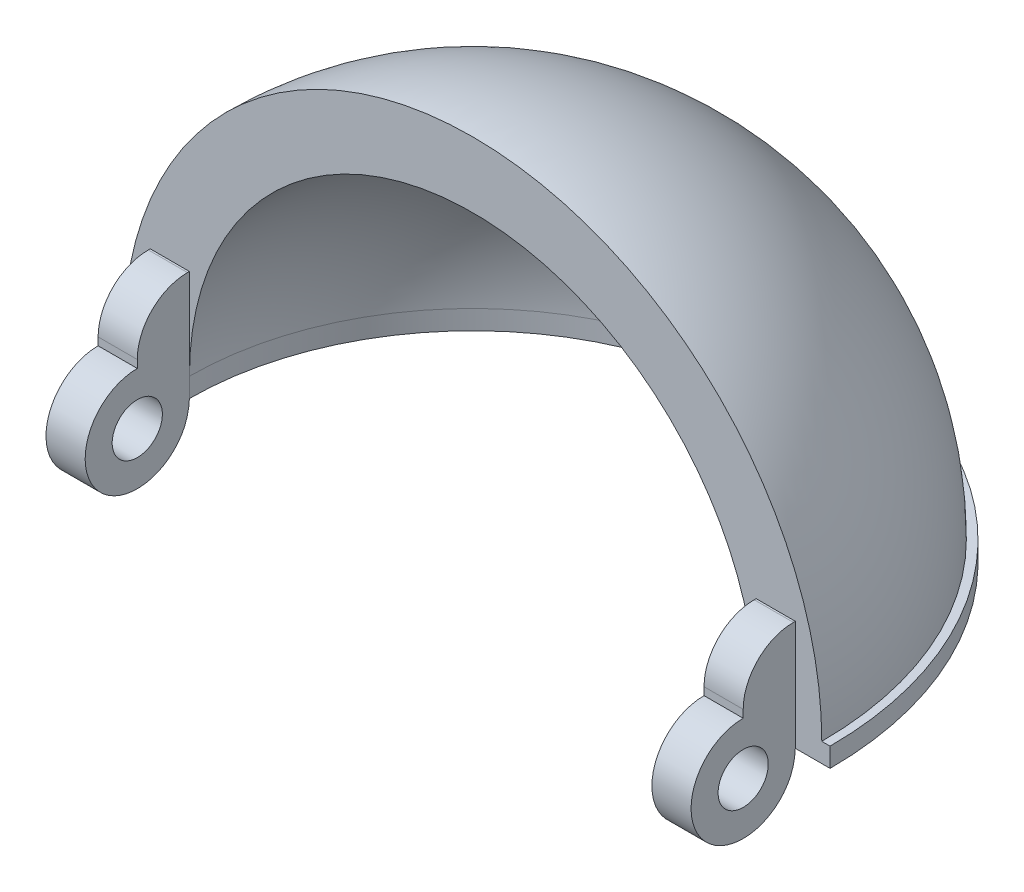
SolidWorks part; units mm, degrees
ref_plane "Front Plane" through (0, 0, 0) normal (0, 0, 1) x (1, 0, 0)
ref_plane "Top Plane" through (0, 0, 0) normal (0, 1, 0) x (1, 0, 0)
ref_plane "Right Plane" through (0, 0, 0) normal (1, 0, 0) x (0, 0, -1)
sketch "Sketch1" plane through (0, 0, 0) normal (0, 1, 0) x (1, 0, 0)
  line L2 (-18.4463, 0) -> (28.559, 0) construction
  line L4 (-18.4463, 0) -> (-13.5837, 0)
  line L8 (23.6964, 0) -> (28.559, 0)
  arc A0 (-18.4463, 0) -> (28.559, 0) centre (5.0564, 0) cw
  arc A1 (-13.5837, 0) -> (23.6964, 0) centre (5.0564, 0) cw
extrude "Boss-Extrude1" add sketch "Sketch1" along normal blind 1.27
sketch "Sketch4" plane through (0, 1.27, 0) normal (0, 1, 0) x (1, 0, 0)
  line L0 (-18.4463, 0) -> (-13.5837, 0) construction
  line L1 (23.6964, 0) -> (28.559, 0) construction
  line L2 (23.6964, 0) -> (28.0144, 0)
  line L3 (-17.9017, 0) -> (-13.5837, 0)
  line L4 (-17.9017, 0) -> (28.0144, 0) construction
  arc A0 (-13.5837, 0) -> (23.6964, 0) centre (5.0564, 0) cw
  arc A1 (-17.9017, 0) -> (28.0144, 0) centre (5.0564, 0) cw
  dimension "D1" = 4.318
  dimension "D2" = 4.318
revolve "Revolve3" add sketch "Sketch4" angle 90 about L4
sketch "Sketch6" plane through (0, 0, 0) normal (0, 0, 1) x (1, 0, 0)
  line L1 (23.6964, 0) -> (28.559, 0)
  line L2 (23.6964, 0) -> (23.6964, 1.27)
  line L3 (23.6964, 1.27) -> (28.559, 1.27)
  line L4 (28.559, 0) -> (28.559, 1.27)
  line L5 (-18.4463, 1.27) -> (-13.5837, 1.27)
  line L6 (-18.4463, 1.27) -> (-18.4463, 0)
  line L7 (-18.4463, 0) -> (-13.5837, 0)
  line L8 (-13.5837, 1.27) -> (-13.5837, 0)
extrude "Boss-Extrude3" add sketch "Sketch6" along normal blind 7.9355 contours L8 L5 L6 L7 | L3 L4 L1 L2 region at (-16.015, 0.635, 0)
sketch "Sketch10" plane through (0, 1.27, 0) normal (0, 1, 0) x (1, 0, 0)
  line L1 (-18.4463, -7.9355) -> (-13.5837, -7.9355)
  line L2 (-18.4463, -7.9355) -> (-18.4463, 0)
  line L3 (-18.4463, 0) -> (-13.5837, 0)
  line L4 (-13.5837, -7.9355) -> (-13.5837, 0)
  line L5 (23.6964, 0) -> (28.559, 0)
  line L6 (23.6964, 0) -> (23.6964, -7.9355)
  line L7 (23.6964, -7.9355) -> (28.559, -7.9355)
  line L8 (28.559, 0) -> (28.559, -7.9355)
extrude "Boss-Extrude4" add sketch "Sketch10" along normal blind 3.81 and the other way blind 6.35
fillet "Fillet7" radius 5.08 1 edges at (-16.015, 5.08, 7.9355) type face fillet first side face at (-16.015, 0, 7.9355) second side face at (-16.3286, 5.08, 3.1742)
fillet "Fillet10" radius 5.08 1 edges at (26.1277, 5.08, 7.9355) type face fillet first side face at (26.4413, 5.08, 3.1742) second side face at (26.1277, 0, 7.9355)
sketch "Sketch13" plane through (-18.4463, 0, 0) normal (-1, 0, 0) x (0, 0, 1)
  line L1 (0, 5.08) -> (2.8555, 5.08) construction
  circle A0 centre (3.4286, 0) radius 1.651
  dimension "D1" = 3.302
  dimension "D2" = 5.08
extrude "Cut-Extrude2" cut sketch "Sketch13" against normal blind 55.372
sketch "Sketch14" plane through (0, 5.08, 0) normal (0, 1, 0) x (1, 0, 0)
  line L1 (28.559, 0) -> (26.273, 0)
  line L2 (28.559, 0) -> (28.559, -11.3681)
  line L3 (28.559, -11.3681) -> (26.273, -11.3681)
  line L4 (26.273, 0) -> (26.273, -11.3681)
  line L5 (-18.4463, 0) -> (-16.1603, 0)
  line L6 (-18.4463, 0) -> (-18.4463, -11.3681)
  line L7 (-18.4463, -11.3681) -> (-16.1603, -11.3681)
  line L8 (-16.1603, 0) -> (-16.1603, -11.3681)
  dimension "D1" = 2.286
  dimension "D2" = 2.286
extrude "Cut-Extrude3" cut sketch "Sketch14" against normal blind 55.372
fillet "Fillet15" 2 edges at (24.9847, -5.08, 7.9355) (24.9847, -5.08, 0) type full round first side face at (24.9847, -2.54, 7.9355) second side face at (24.9847, -2.54, 0) middle face at (24.9847, -5.08, 3.9678)
fillet "Fillet16" 2 edges at (-14.872, -5.08, 0) (-14.872, -5.08, 7.9355) type full round first side face at (-14.872, -2.54, 0) second side face at (-14.872, -2.54, 7.9355) middle face at (-14.872, -5.08, 3.9678)
sketch "Sketch16" plane through (26.273, 0, 0) normal (1, 0, 0) x (0, 0, -1)
  line L0 (-7.9355, -1.1122) -> (-7.9355, 0) construction
  arc A1 (0, 0) -> (-7.9355, -0.5561) centre (-3.9961, 0.1259) cw
  arc A2 (0, 0) -> (-7.9355, -0.5561) centre (-3.9138, -1.048) cw
extrude "Cut-Extrude4" cut sketch "Sketch16" against normal blind 55.372 body kept at (-13.5837, 0, 7.9355)
sketch "Sketch18" plane through (26.273, 0, 0) normal (1, 0, 0) x (0, 0, -1)
  line L0 (-3.4286, 3.4286) -> (0, 3.4286)
  line L1 (0, 3.4286) -> (0, 5.4674)
  line L2 (0, 5.4674) -> (-9.0316, 5.4674)
  line L3 (-9.0316, 5.4674) -> (-9.0316, -4.4868)
  line L4 (-9.0316, -4.4868) -> (0, -4.4868)
  line L5 (0, -4.4868) -> (0, 0)
  arc A0 (-3.4286, 3.4286) -> (0, 0) centre (-3.4286, 0) ccw
extrude "Cut-Extrude7" cut sketch "Sketch18" against normal blind 55.88
sketch "Sketch19" plane through (0, 3.4286, 0) normal (0, 1, 0) x (1, 0, 0)
  line L1 (23.6964, 0) -> (26.273, 0)
  line L2 (23.6964, 0) -> (23.6964, -3.4286)
  line L3 (23.6964, -3.4286) -> (26.273, -3.4286)
  line L4 (26.273, 0) -> (26.273, -3.4286)
  line L5 (-16.1603, 0) -> (-13.5837, 0)
  line L6 (-16.1603, 0) -> (-16.1603, -3.4286)
  line L7 (-16.1603, -3.4286) -> (-13.5837, -3.4286)
  line L8 (-13.5837, 0) -> (-13.5837, -3.4286)
extrude "Boss-Extrude5" add sketch "Sketch19" along normal blind 3.81
fillet "Fillet17" radius 3.302 1 edges at (24.9847, 7.2386, 3.4286) type face fillet first side face at (24.9847, 7.2386, 1.7143) second side face at (24.9847, 5.3336, 3.4286)
fillet "Fillet18" radius 3.302 1 edges at (-14.872, 7.2386, 3.4286) type face fillet first side face at (-14.872, 5.3336, 3.4286) second side face at (-14.872, 7.2386, 1.7143)
